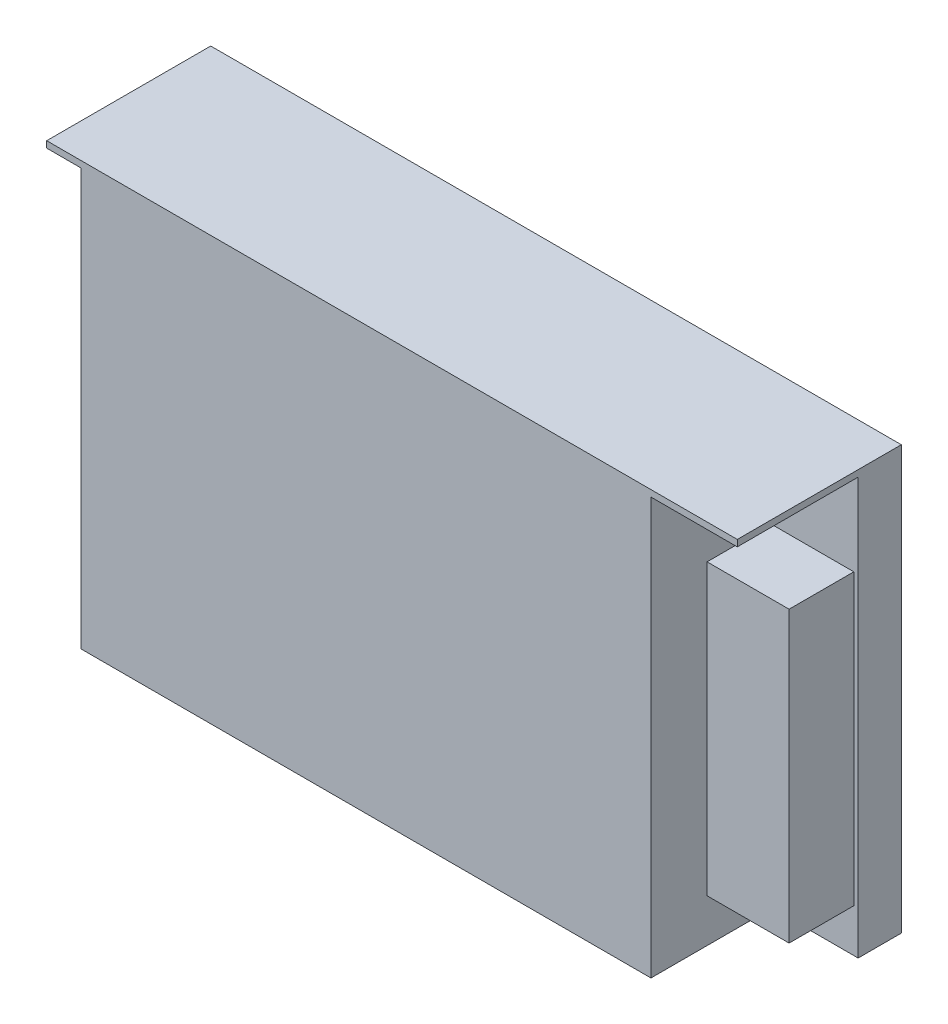
SolidWorks part; units mm, degrees
material "镀铬不锈钢"
ref_plane "前视基准面" through (0, 0, 0) normal (0, 0, 1) x (1, 0, 0)
ref_plane "上视基准面" through (0, 0, 0) normal (0, 1, 0) x (1, 0, 0)
ref_plane "右视基准面" through (0, 0, 0) normal (1, 0, 0) x (0, 0, -1)
sketch "草图1" plane through (0, 0, 0) normal (0, 0, 1) x (1, 0, 0)
  line L1 (0, 0) -> (160, 0)
  line L2 (0, 0) -> (0, 98)
  line L3 (0, 98) -> (160, 98)
  line L4 (160, 0) -> (160, 98)
  dimension "D1" = 160
  dimension "D2" = 98
extrude "凸台-拉伸1" add sketch "草图1" along normal blind 38
sketch "草图2" plane through (0, 0, 38) normal (0, 0, 1) x (1, 0, 0)
  line L0 (0, 0) -> (160, 0) construction
  line L1 (160, 96.5) -> (140, 96.5)
  line L2 (160, 96.5) -> (160, 0)
  line L3 (160, 0) -> (140, 0)
  line L4 (140, 96.5) -> (140, 0)
  line L6 (160, 98) -> (0, 98) construction
  dimension "D1" = 20
  dimension "D2" = 1.5
extrude "切除-拉伸1" cut sketch "草图2" against normal blind 28
sketch "草图3" plane through (0, 0, 10) normal (0, 0, 1) x (1, 0, 0)
  line L0 (140, 96.5) -> (140, 0) construction
  line L1 (140, 10) -> (159, 10)
  line L2 (140, 10) -> (140, 77)
  line L3 (140, 77) -> (159, 77)
  line L4 (159, 10) -> (159, 77)
  line L5 (140, 0) -> (160, 0) construction
  dimension "D1" = 67
  dimension "D2" = 19
  dimension "D3" = 10
extrude "凸台-拉伸2" add sketch "草图3" along normal blind 15
sketch "草图4" plane through (0, 0, 0) normal (-1, 0, 0) x (0, 0, 1)
  line L0 (38, 98) -> (0, 98) construction
  line L1 (38, 0) -> (22, 0)
  line L2 (38, 0) -> (38, 96.5)
  line L3 (38, 96.5) -> (22, 96.5)
  line L4 (22, 0) -> (22, 96.5)
  dimension "D1" = 16
  dimension "D2" = 1.5
extrude "切除-拉伸2" cut sketch "草图4" against normal blind 8
chamfer "倒角1" distance 8 angle 45 1 edges at (8, 48.25, 22)
sketch "草图5" plane through (0, 0, 0) normal (0, -1, 0) x (1, 0, 0)
  line L0 (0, 22) -> (8, 30)
  line L1 (8, 30) -> (8, 1.5)
  line L3 (8, 1.5) -> (0, 1.5)
  line L4 (0, 1.5) -> (0, 22)
  line L5 (0, 0) -> (160, 0) construction
  dimension "D1" = 1.5
extrude "切除-拉伸3" cut sketch "草图5" against normal blind 10
